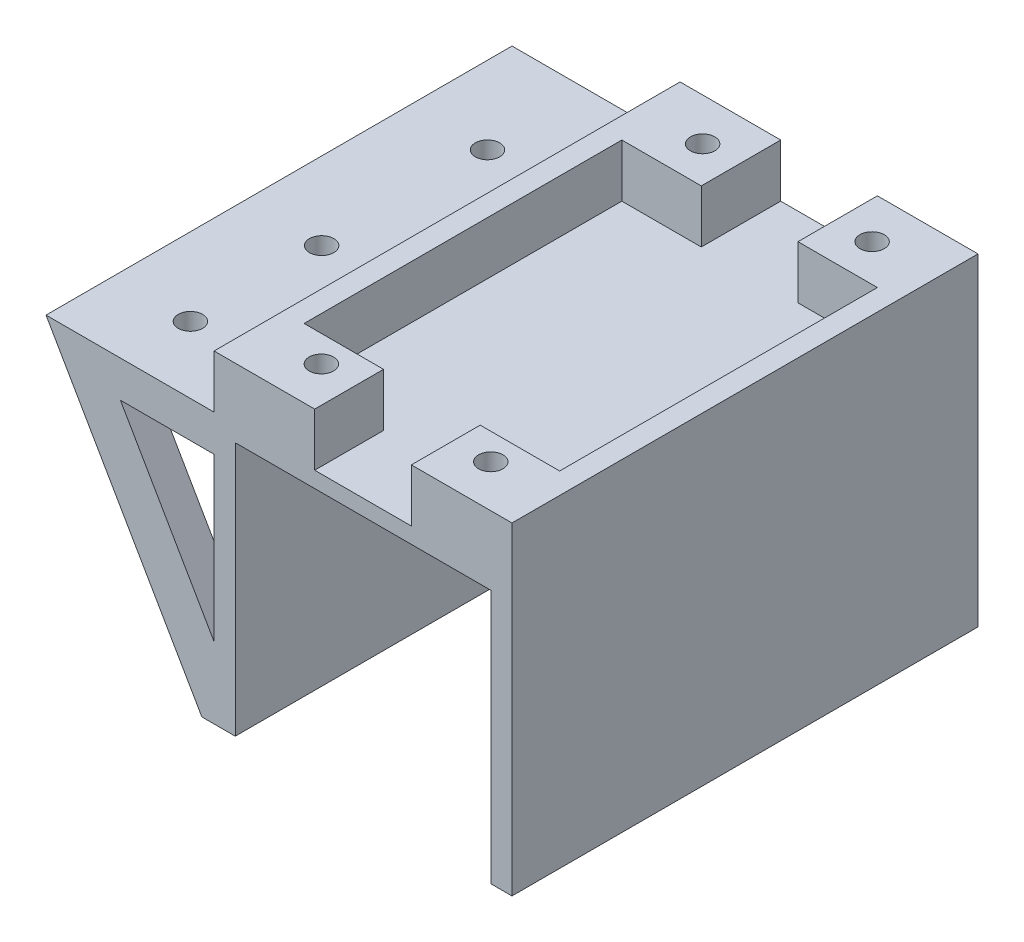
SolidWorks part; units mm, degrees
ref_plane "Front" through (0, 0, 0) normal (0, 0, 1) x (1, 0, 0)
ref_plane "Top" through (0, 0, 0) normal (0, 1, 0) x (1, 0, 0)
ref_plane "Right" through (0, 0, 0) normal (1, 0, 0) x (0, 0, -1)
sketch "Sketch1" plane through (0, 0, 0) normal (0, 0, 1) x (1, 0, 0)
  line L0 (0, 0) -> (0, 70)
  line L1 (0, 70) -> (56.254, 70)
  line L2 (56.254, 70) -> (56.254, 0)
  line L3 (56.254, 0) -> (52.254, 0)
  line L4 (52.254, 0) -> (52.254, 65)
  line L5 (52.254, 65) -> (4, 65)
  line L6 (4, 65) -> (4, 0)
  line L7 (4, 0) -> (0, 0)
  line L9 (4, 55) -> (52.254, 55)
  line L10 (4, 55) -> (4, 52)
  line L11 (4, 52) -> (52.254, 52)
  line L12 (52.254, 55) -> (52.254, 52)
  dimension "D1" = 48.254
  dimension "D2" = 4
  dimension "D3" = 4
  dimension "D4" = 5
  dimension "D5" = 70
  dimension "D6" = 3
  dimension "D7" = 10
extrude "Boss-Extrude1" add sketch "Sketch1" along normal blind 70 contours L7 L6 L5 L4 L3 L2 L1 L0 | L9 L12 L11 L10 region at (0.898, 35, 0)
sketch "Sketch3" plane through (0, 0, 70) normal (0, 0, 1) x (1, 0, 0)
  line L0 (0, 70) -> (-40.3946, 70)
  line L1 (-40.3946, 70) -> (0, 0.0344)
  line L2 (0, 0) -> (0, 70) construction
  line L3 (0, 0.0344) -> (0, 70)
  line L4 (0, 70) -> (0, 62.5)
  line L5 (0, 62.5) -> (-26, 62.5)
  line L6 (-26, 62.5) -> (0, 17.4667)
  line L7 (0, 17.4667) -> (0, 0.0344)
  line M11 (0, 70) -> (0, 0)
  dimension "D1" = 60
  dimension "D2" = 180
  dimension "D3" = 7.5
  dimension "D4" = 26
extrude "Boss-Extrude3" add sketch "Sketch3" against normal blind 8 contours L6 L5 L0 L1 M11 region at (-16.8587, 46.1047, 70)
sketch "Sketch4" plane through (0, 0, 0) normal (0, 0, -1) x (-1, 0, 0)
  line L0 (0, 70) -> (40.3946, 70)
  line L1 (40.3946, 70) -> (0, 0)
  line L2 (0, 0) -> (0, 17.4667)
  line L3 (0, 17.4667) -> (26, 62.5)
  line L4 (26, 62.5) -> (0, 62.5)
  line L5 (0, 62.5) -> (0, 70)
extrude "Boss-Extrude4" add sketch "Sketch4" against normal blind 8
ref_plane "Plane1" through (0, 0, 39) normal (0, 0, -1) x (-1, 0, 0)
sketch "Sketch5" plane through (0, 0, 39) normal (0, 0, -1) x (-1, 0, 0)
  line L0 (0, 62.5) -> (0, 70)
  line L1 (0, 70) -> (40.3946, 70)
  line L2 (40.3946, 70) -> (0, 0)
  line L3 (0, 0) -> (0, 17.4667)
  line L4 (0, 17.4667) -> (26, 62.5)
  line L5 (26, 62.5) -> (0, 62.5)
extrude "Boss-Extrude5" add sketch "Sketch5" along normal blind 8
sketch "Sketch6" plane through (0, 0, 0) normal (0, 0, -1) x (-1, 0, 0)
  line L5 (0, 62.5) -> (36.0666, 62.5)
  line L6 (0, 0) -> (40.3946, 70) construction
  line L7 (36.0666, 62.5) -> (40.3946, 70)
  line L8 (40.3946, 70) -> (0, 70)
  line L9 (40.3946, 70) -> (-56.254, 70) construction
  line L10 (0, 70) -> (0, 62.5)
  line L11 (-4, 0) -> (0, 0)
  line L12 (0, 0) -> (7.5019, 13)
  line L13 (7.5019, 13) -> (-4, 13)
  line L14 (-4, 52) -> (-4, 0) construction
  line L15 (-4, 13) -> (-4, 0)
  dimension "D1" = 13
extrude "Boss-Extrude6" add sketch "Sketch6" against normal blind 70
sketch "Sketch7" plane through (0, 0, 70) normal (0, 0, 1) x (1, 0, 0)
  line L0 (0, 17.4667) -> (0, 62.5) construction
  line L1 (-40.3946, 70) -> (0, 70)
  line L2 (-40.3946, 70) -> (-40.3946, 53)
  line L3 (-40.3946, 53) -> (0, 53)
  line L4 (0, 70) -> (0, 53)
  dimension "D1" = 17
extrude "Cut-Extrude3" cut sketch "Sketch7" against normal blind 70
sketch "Sketch8" plane through (0, 0, 0) normal (0, 0, -1) x (-1, 0, 0)
  line L1 (-4, 55) -> (-4, 52)
  line L2 (-4, 52) -> (-52.254, 52) construction
  line L3 (-4, 52) -> (30.0074, 52)
  line L4 (0, 0) -> (30.5845, 53) construction
  line L6 (30.0074, 52) -> (31.7386, 55)
  line L7 (31.7386, 55) -> (-4, 55)
  dimension "D1" = 180
extrude "Boss-Extrude7" add sketch "Sketch8" against normal blind 70
sketch "Sketch11" plane through (0, 0, 70) normal (0, 0, 1) x (1, 0, 0)
  line L0 (-31.7386, 55) -> (0, 0)
  line L3 (-31.7386, 55) -> (0, 55) construction
  line L4 (-27.289, 55) -> (-31.7386, 55)
  line L5 (-27.289, 55) -> (-3.0537, 13)
  line L6 (-3.0537, 13) -> (0, 0)
extrude "Boss-Extrude10" add sketch "Sketch11" against normal blind 8
sketch "Sketch12" plane through (0, 0, 70) normal (0, 0, 1) x (1, 0, 0)
  line L0 (-31.7386, 55) -> (-27.7598, 48.1051)
  line L1 (0, 0) -> (-31.7386, 55) construction
  line L2 (-27.7598, 48.1051) -> (0, 48.1051)
  line L3 (0, 17.4667) -> (0, 52) construction
  line L4 (0, 48.1051) -> (0, 55)
  line L5 (0, 55) -> (-31.7386, 55)
extrude "Boss-Extrude11" add sketch "Sketch12" against normal blind 70
sketch "Sketch13" plane through (0, 0, 0) normal (0, -1, 0) x (1, 0, 0)
  line L1 (67.4394, -10.6205) -> (-15.562, -10.6205)
  line L2 (67.4394, -10.6205) -> (67.4394, 77.2481)
  line L3 (67.4394, 77.2481) -> (-15.562, 77.2481)
  line L4 (-15.562, -10.6205) -> (-15.562, 77.2481)
extrude "Cut-Extrude4" cut sketch "Sketch13" against normal blind 4
sketch "Sketch14" plane through (0, 0, 70) normal (0, 0, 1) x (1, 0, 0)
  line L0 (-2.3083, 4) -> (-31.7386, 55)
  line L1 (-31.7386, 55) -> (0, 55)
  line L2 (0, 55) -> (0, 70)
  line L3 (0, 70) -> (56.254, 70)
  line L4 (56.254, 70) -> (56.254, 4)
  line L5 (56.254, 4) -> (52.254, 4)
  line L6 (52.254, 4) -> (52.254, 52)
  line L7 (52.254, 52) -> (4, 52)
  line L8 (4, 52) -> (4, 4)
  line L9 (4, 4) -> (-2.3083, 4)
  line L14 (-17.6891, 48.1051) -> (0, 48.1051)
  line L15 (52.254, 55) -> (4, 55)
  line L16 (52.254, 55) -> (52.254, 65)
  line L17 (52.254, 65) -> (4, 65)
  line L18 (4, 55) -> (4, 65)
  line L19 (-17.6891, 48.1051) -> (0, 48.1051) construction
  line L20 (0, 48.1051) -> (0, 17.4667)
  line L21 (0, 17.4667) -> (-17.6891, 48.1051)
extrude "Boss-Extrude12" add sketch "Sketch14" along normal blind 20
sketch "Sketch15" plane through (0, 0, 90) normal (0, 0, 1) x (1, 0, 0)
  line L0 (56.254, 4) -> (56.254, 70) construction
  line L1 (56.254, 65) -> (37.264, 65)
  line L2 (56.254, 65) -> (56.254, 55)
  line L3 (56.254, 55) -> (37.264, 55)
  line L4 (37.264, 65) -> (37.264, 55)
  line L5 (4, 55) -> (52.254, 55) construction
  dimension "D1" = 18.99
sketch "Sketch16" plane through (0, 0, 90) normal (0, 0, 1) x (1, 0, 0)
  line L1 (0, 70) -> (56.254, 70)
  line L2 (0, 70) -> (0, 65)
  line L3 (0, 65) -> (56.254, 65)
  line L4 (56.254, 70) -> (56.254, 65)
extrude "Cut-Extrude5" cut sketch "Sketch16" against normal blind 100
sketch "Sketch17" plane through (0, 65, 0) normal (0, 1, 0) x (1, 0, 0)
  line L1 (52.254, 0) -> (37.254, 0)
  line L2 (52.254, 0) -> (52.254, -15)
  line L3 (52.254, -15) -> (37.254, -15)
  line L4 (37.254, 0) -> (37.254, -15)
  line L5 (52.254, -90) -> (37.254, -90)
  line L6 (52.254, -90) -> (52.254, -75)
  line L7 (52.254, -75) -> (37.254, -75)
  line L8 (37.254, -90) -> (37.254, -75)
  dimension "D1" = 15
  dimension "D2" = 15
  dimension "D3" = 15
  dimension "D4" = 15
extrude "Boss-Extrude14" add sketch "Sketch17" against normal blind 13
sketch "Sketch21" plane through (0, 52, 0) normal (0, -1, 0) x (-1, 0, 0)
  circle A0 centre (-44.254, -80) radius 2.3
  circle A1 centre (-44.254, -8) radius 2.3
sketch "Sketch22" plane through (0, 52, 0) normal (0, -1, 0) x (1, 0, 0)
  line L1 (48.0965, 6.0036) -> (47.9041, 10.3295)
  line L2 (47.9041, 10.3295) -> (44.0617, 12.3259)
  line L3 (44.0617, 12.3259) -> (40.4115, 9.9964)
  line L4 (40.4115, 9.9964) -> (40.6039, 5.6705)
  line L5 (40.6039, 5.6705) -> (44.4463, 3.6741)
  line L6 (44.4463, 3.6741) -> (48.0965, 6.0036)
  line L7 (45.2007, 75.7746) -> (48.3866, 78.7072)
  line L8 (48.3866, 78.7072) -> (47.4399, 82.9325)
  line L9 (47.4399, 82.9325) -> (43.3073, 84.2254)
  line L10 (43.3073, 84.2254) -> (40.1214, 81.2928)
  line L11 (40.1214, 81.2928) -> (41.0681, 77.0675)
  line L12 (41.0681, 77.0675) -> (45.2007, 75.7746)
  circle A0 centre (44.254, 8) radius 3.75 construction
  circle A1 centre (44.254, 80) radius 3.75 construction
  point P10 (42.2366, 11.1611)
  dimension "D1" = 7.5
  dimension "D2" = 7.5
extrude "Cut-Extrude8" cut sketch "Sketch22" against normal blind 5
extrude "Cut-Extrude9" cut sketch "Sketch21" against normal blind 15
sketch "Sketch23" plane through (0, 0, 0) normal (-0.8661, -0.4998, 0) x (0, 0, 1)
  line L0 (90, 63.5007) -> (90, 4.6182) construction
  line L1 (70, 55.5401) -> (82, 55.5401)
  line L2 (70, 55.5401) -> (70, 15.0093)
  line L3 (70, 15.0093) -> (82, 15.0093)
  line L4 (82, 55.5401) -> (82, 15.0093)
  line L5 (62, 55.5401) -> (62, 15.0093) construction
  dimension "D1" = 8
  dimension "D2" = 8
extrude "Cut-Extrude10" cut sketch "Sketch23" against normal blind 9
sketch "Sketch25" plane through (0, 48.1051, 0) normal (0, -1, 0) x (-1, 0, 0)
  circle A0 centre (17.0755, -19.3006) radius 2.3
  circle A1 centre (17.0755, -50.6137) radius 2.3
extrude "Cut-Extrude11" cut sketch "Sketch25" against normal blind 20
sketch "Sketch26" plane through (0, 48.1051, 0) normal (0, -1, 0) x (1, 0, 0)
  circle A0 centre (-17.0755, 75.3913) radius 2.3
extrude "Cut-Extrude12" cut sketch "Sketch26" against normal blind 20
sketch "Sketch27" plane through (0, 0, 90) normal (0, 0, 1) x (1, 0, 0)
  line L0 (-23.3104, 48.1051) -> (-27.7598, 48.1051)
  line L1 (-31.7386, 55) -> (-2.3083, 4) construction
  line L2 (-27.7598, 48.1051) -> (-31.7386, 55)
  line L3 (-31.7386, 55) -> (-23.3104, 55)
  line L4 (0, 55) -> (-31.7386, 55) construction
  line L5 (-23.3104, 55) -> (-23.3104, 48.1051)
extrude "Boss-Extrude16" add sketch "Sketch27" against normal blind 20
sketch "Sketch28" plane through (0, 55, 0) normal (0, 1, 0) x (1, 0, 0)
  line L0 (4, -90) -> (37.254, -90) construction
  line L1 (4, 0) -> (19, 0)
  line L2 (4, 0) -> (4, -15)
  line L3 (4, -15) -> (19, -15)
  line L4 (19, 0) -> (19, -15)
  line L5 (4, -90) -> (19, -90)
  line L6 (4, -90) -> (4, -75)
  line L7 (4, -75) -> (19, -75)
  line L8 (19, -90) -> (19, -75)
  line L9 (4, 0) -> (4, -90) construction
  dimension "D1" = 15
  dimension "D2" = 15
  dimension "D3" = 15
  dimension "D4" = 15
extrude "Boss-Extrude17" add sketch "Sketch28" along normal blind 10
sketch "Sketch29" plane through (0, 52, 0) normal (0, -1, 0) x (-1, 0, 0)
  circle A0 centre (-12.254, -8) radius 2.3
  circle A1 centre (-12.254, -80) radius 2.3
extrude "Cut-Extrude13" cut sketch "Sketch29" against normal blind 20
sketch "Sketch30" plane through (0, 48.1051, 0) normal (0, -1, 0) x (1, 0, 0)
  line L1 (-27.7598, 70) -> (-17.3688, 70)
  line L2 (-27.7598, 70) -> (-27.7598, 82)
  line L3 (-27.7598, 82) -> (-17.3688, 82)
  line L4 (-17.3688, 70) -> (-17.3688, 82)
extrude "Boss-Extrude18" add sketch "Sketch30" against normal blind 5
sketch "Sketch31" plane through (0, 48.1051, 0) normal (0, -1, 0) x (1, 0, 0)
  circle A0 centre (-17.0755, 75.3913) radius 2.3
extrude "Cut-Extrude14" cut sketch "Sketch31" against normal blind 45
sketch "Sketch33" plane through (0, 55, 0) normal (0, 1, 0) x (1, 0, 0)
  circle A0 centre (27.6164, -46.5233) radius 1
  circle A1 centre (26.8974, -20.9206) radius 1
  circle A2 centre (28.9102, -66.6327) radius 1
  circle A3 centre (-20.9687, -5.2719) radius 1
  circle A4 centre (-23.4497, -23.5026) radius 1
  circle A5 centre (-17.8546, -42.0102) radius 1
  circle A6 centre (-22.4497, -64.7625) radius 1
  circle A7 centre (-17.8546, -85.6157) radius 1
ref_plane "Plane2" through (-31.7386, 55, 90) normal (0.4998, -0.8661, 0) x (-0.8661, -0.4998, 0)
sketch "Sketch36" plane through (0, 0, 90) normal (0, 0, 1) x (1, 0, 0)
  circle A0 centre (23.0361, 36.9328) radius 60.0365
extrude "Cut-Extrude15" cut sketch "Sketch36" against normal blind 2
